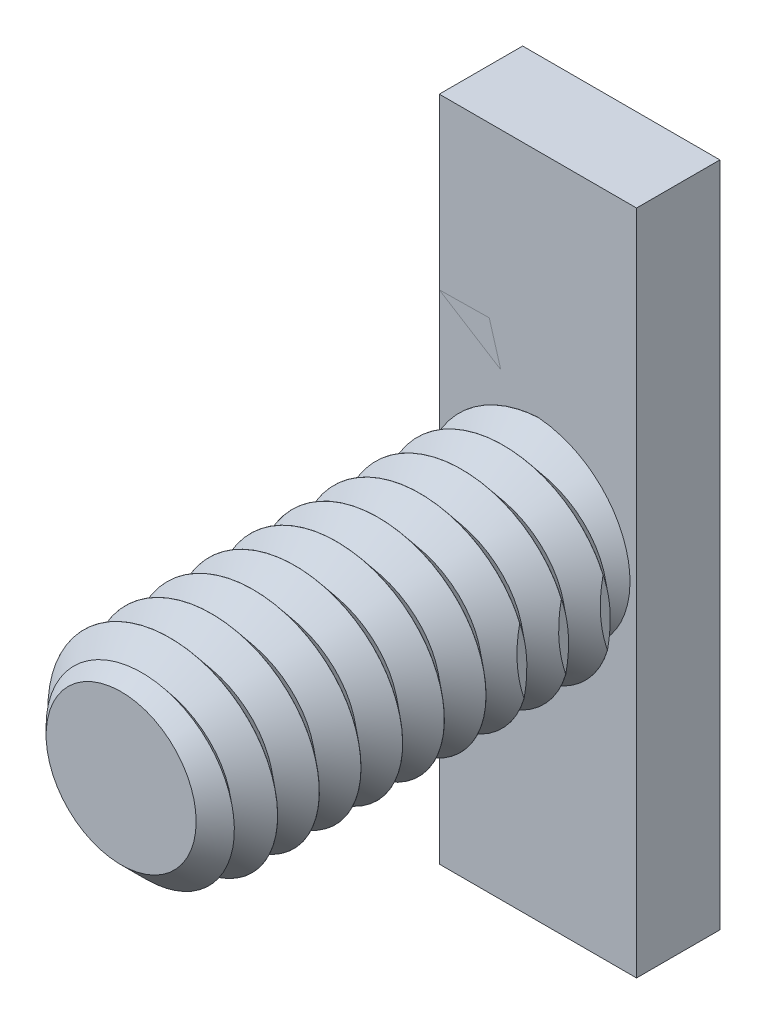
SolidWorks part; units mm, degrees
ref_plane "Front Plane" through (0, 0, 0) normal (0, 0, 1) x (1, 0, 0)
ref_plane "Top Plane" through (0, 0, 0) normal (0, 1, 0) x (1, 0, 0)
ref_plane "Right Plane" through (0, 0, 0) normal (1, 0, 0) x (0, 0, -1)
sketch "Sketch1" plane through (0, 0, 0) normal (0, 0, 1) x (1, 0, 0)
  line L1 (4.7324, -7.9333) -> (9.2367, 0.1318)
  line L2 (9.2367, 0.1318) -> (4.5042, 8.0651)
  line L3 (4.5042, 8.0651) -> (-4.7324, 7.9333)
  line L4 (-4.7324, 7.9333) -> (-9.2367, -0.1318)
  line L5 (-9.2367, -0.1318) -> (-4.5042, -8.0651)
  line L6 (-4.5042, -8.0651) -> (4.7324, -7.9333)
  circle A0 centre (0, 0) radius 8 construction
  dimension "D1" = 16
extrude "Boss-Extrude1" add sketch "Sketch1" along normal blind 4
sketch "Sketch2" plane through (0, 0, 4) normal (0, 0, 1) x (1, 0, 0)
  circle A0 centre (0, 0) radius 5
  dimension "D1" = 10
extrude "Boss-Extrude2" add sketch "Sketch2" along normal blind 20
sketch "Sketch3" plane through (0, 0, 24) normal (0, 0, 1) x (1, 0, 0)
  circle A0 centre (0, 0) radius 3.8
  dimension "D1" = 7.6
curve "Helix/Spiral1" pitch 2 height 21 turns 10.5
chamfer "Chamfer1" distance 1.4 angle 45 1 edges at (5, 0, 24)
sketch "Sketch15" plane through (0, 0, 0) normal (1, 0, 0) x (0, 0, -1)
  line L0 (-24, -3.8) -> (-24.9975, -5)
  line L5 (-24.9975, -5) -> (-23.0025, -5)
  line L6 (-4, -5) -> (-22.6, -5) construction
  line L7 (-22.6, 5) -> (-22.6, -5) construction
  line L9 (-4, 5) -> (-4, -5) construction
  line L10 (-4, -5) -> (-4, -7.9992) construction
  line L11 (-4, -8.0651) -> (-4, -7.9333) construction
  line L12 (-23.0025, -5) -> (-24, -3.8)
  point P16 (-4, -7.9992)
  dimension "D1" = 1.2
  dimension "D2" = 1.995
  dimension "D3" = 1.2
sweep "Cut-Sweep1" cut profiles "Sketch15" path "Helix/Spiral1"
sketch "Sketch22" plane through (0, 0, 0) normal (0, 0, -1) x (-1, 0, 0)
  line L6 (-4.7324, -7.9333) -> (4.5042, -8.0651)
  line L7 (4.5042, -8.0651) -> (9.2367, -0.1318)
  line L8 (9.2367, -0.1318) -> (4.7324, 7.9333)
  line L9 (4.7324, 7.9333) -> (-4.5042, 8.0651)
  line L10 (-4.5042, 8.0651) -> (-9.2367, 0.1318)
  line L11 (-9.2367, 0.1318) -> (-4.7324, -7.9333)
  line L12 (-4.7324, -7.9333) -> (4.5042, -8.0651)
  line L13 (4.5042, -8.0651) -> (9.2367, -0.1318)
  line L14 (9.2367, -0.1318) -> (4.7324, 7.9333)
  line L15 (4.7324, 7.9333) -> (-4.5042, 8.0651)
  line L16 (-4.5042, 8.0651) -> (-9.2367, 0.1318)
  line L17 (-9.2367, 0.1318) -> (-4.7324, -7.9333)
  dimension "D1" = 0
extrude "Boss-Extrude3" add sketch "Sketch22" against normal up to surface (4 mm away) up to face at (0, 0, 4)
sketch "Sketch23" plane through (0, 0, 0) normal (1, 0, 0) x (0, 0, -1)
  line L0 (-2, -7.9333) -> (-2, -15.9333) construction
  line L1 (-4, -15.9333) -> (0, -15.9333)
  line L2 (-4, -15.9333) -> (-4, 16.0651)
  line L3 (-4, 16.0651) -> (0, 16.0651)
  line L4 (0, -15.9333) -> (0, 16.0651)
  line L5 (-4, 8.0651) -> (0, 8.0651) construction
  line L6 (-2, 8.0651) -> (-2, 16.0651) construction
  line L7 (-4, -7.9333) -> (0, -7.9333) construction
  dimension "D1" = 8
extrude "Boss-Extrude4" add sketch "Sketch23" along normal up to vertex (4.7324 mm away) separate body
mirror "Mirror1" about plane through (0, 0, 0) normal (-1, 0, 0) of bodies 141
sketch "Sketch26" plane through (0, 0, 0) normal (0, 0, -1) x (-1, 0, 0)
  line L0 (-4.7324, -15.9333) -> (-4.7324, 16.0651)
  line L1 (-4.7324, 16.0651) -> (4.7324, 16.0651)
  line L2 (4.7324, -15.9333) -> (4.7324, 16.0651) construction
  line L3 (-4.7324, 16.0651) -> (4.7324, 16.0651) construction
  line L4 (4.7324, 16.0651) -> (4.7324, -15.9333)
  line L5 (4.7324, -15.9333) -> (-4.7324, -15.9333)
  line L6 (-18.2716, -24.1969) -> (-12.165, 25.3849)
  line L7 (-12.165, 25.3849) -> (24.4399, 24.8106)
  line L8 (24.4399, 24.8106) -> (10.0357, -20.1819)
  line L9 (10.0357, -20.1819) -> (-18.2716, -24.1969)
extrude "Cut-Extrude1" cut sketch "Sketch26" against normal blind 10
